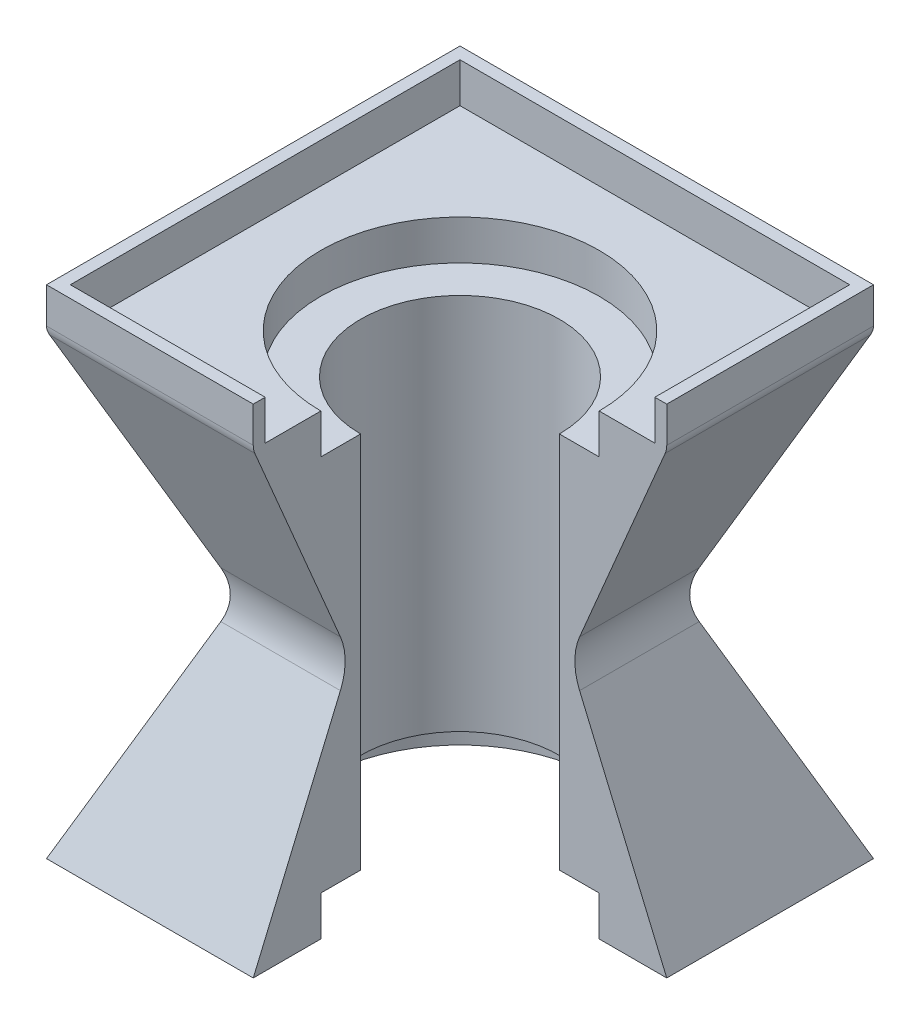
SolidWorks part; units mm, degrees
material "Cast Stainless Steel"
ref_plane "Front Plane" through (0, 0, 0) normal (0, 0, 1) x (1, 0, 0)
ref_plane "Top Plane" through (0, 0, 0) normal (0, 1, 0) x (1, 0, 0)
ref_plane "Right Plane" through (0, 0, 0) normal (1, 0, 0) x (0, 0, -1)
sketch "Sketch1" plane through (0, 0, 0) normal (0, 1, 0) x (1, 0, 0)
  line L1 (-52, 52) -> (52, 52)
  line L2 (-52, 52) -> (-52, -52)
  line L3 (-52, -52) -> (52, -52)
  line L4 (52, 52) -> (52, -52)
  line L5 (-52, 52) -> (52, -52) construction
  line L6 (-52, -52) -> (52, 52) construction
  point P0 (0, 0)
  dimension "D1" = 104
  dimension "D2" = 104
extrude "Boss-Extrude1" add sketch "Sketch1" along normal blind 57.5 draft 23
mirror "Mirror1" about plane through (0, 57.5, 0) normal (0, 1, 0) of bodies 101
sketch "Sketch2" plane through (0, 115, 0) normal (0, 1, 0) x (1, 0, 0)
  circle A0 centre (0, 0) radius 25
  point P3 (0, 0)
  dimension "D1" = 50
extrude "Cut-Extrude2" cut sketch "Sketch2" against normal through all
sketch "Sketch3" plane through (0, 115, 0) normal (0, 1, 0) x (1, 0, 0)
  circle A0 centre (0, 0) radius 35
  dimension "D1" = 70
extrude "Cut-Extrude4" cut sketch "Sketch3" against normal blind 10
sketch "Sketch4" plane through (0, 0, 0) normal (0, -1, 0) x (1, 0, 0)
  circle A0 centre (0, 0) radius 35
  dimension "D1" = 70
extrude "Cut-Extrude5" cut sketch "Sketch4" against normal blind 10
sketch "Sketch5" plane through (0, 115, 0) normal (0, 1, 0) x (1, 0, 0)
  line L0 (0, 55.5964) -> (0, -59.0964) construction
  line L1 (-59.9714, 0) -> (72.6254, 0) construction
  line L3 (0, 0) -> (52, 0)
  line L4 (0, 0) -> (0, -52)
  line L5 (0, -52) -> (52, -52)
  line L6 (52, 0) -> (52, -52)
extrude "Cut-Extrude6" cut sketch "Sketch5" against normal through all
fillet "Fillet1" radius 15 4 edges at (27.5927, 57.5, -13.7963) (0, 57.5, -27.5927) (-27.5927, 57.5, 0) (-13.7963, 57.5, 27.5927)
sketch "Sketch6" plane through (0, 115, 0) normal (0, 1, 0) x (1, 0, 0)
  line L0 (49, 3) -> (49, 0)
  line L1 (52, 0) -> (35, 0) construction
  line L2 (49, 0) -> (52, 0)
  line L8 (0, -49) -> (0, -52)
  line L10 (-3, -49) -> (0, -49)
  line L11 (0, -35) -> (0, -52) construction
  line L12 (-49, -49) -> (-3, -49)
  line L13 (-3, -49) -> (-3, -37.8814)
  line L14 (37.8814, 3) -> (49, 3)
  line L15 (49, 3) -> (49, 49)
  line L16 (49, 49) -> (-49, 49)
  line L17 (-49, 49) -> (-49, -49)
  line L18 (-49, -49) -> (-3, -49)
  line L21 (49, 3) -> (49, 49)
  line L22 (49, 49) -> (-49, 49)
  line L23 (-49, 49) -> (-49, -49)
  line L24 (0, -52) -> (-52, -52)
  line L25 (-52, -52) -> (-52, 52)
  line L26 (-52, 52) -> (52, 52)
  line L27 (52, 52) -> (52, 0)
  arc A2 (37.8814, 3) -> (-3, -37.8814) centre (0, 0) ccw
  dimension "D1" = 3
extrude "Boss-Extrude3" add sketch "Sketch6" along normal blind 10
fillet "Fillet2" radius 5 4 edges at (52, 115, -26) (0, 115, -52) (-52, 115, 0) (-26, 115, 52)
sketch "Sketch7" plane through (0, 115, 0) normal (0, 1, 0) x (1, 0, 0)
  line L0 (0, 55.731) -> (0, -58.4234) construction
  line L1 (-58.4907, 0) -> (64.0099, 0) construction
  line L3 (-40.6586, 40.6586) -> (-30.052, 30.052) construction
  line L6 (-38.5373, 42.78) -> (-27.9307, 32.1734)
  line L7 (-42.78, 38.5373) -> (-32.1734, 27.9307)
  circle A2 centre (0, 0) radius 50 construction
  arc A3 (-38.5373, 42.78) -> (-42.78, 38.5373) centre (-40.6586, 40.6586) ccw
  arc A4 (-32.1734, 27.9307) -> (-27.9307, 32.1734) centre (-30.052, 30.052) ccw
  point P9 (-35.3553, 35.3553)
  dimension "D2" = 3
  dimension "D3" = 100
  dimension "D4" = 26.7965
  dimension "D1" = 15
equation "\"A\"= 115.00mm"
equation "\"B\" = 104mm"
equation "\"C\"= 23deg"
